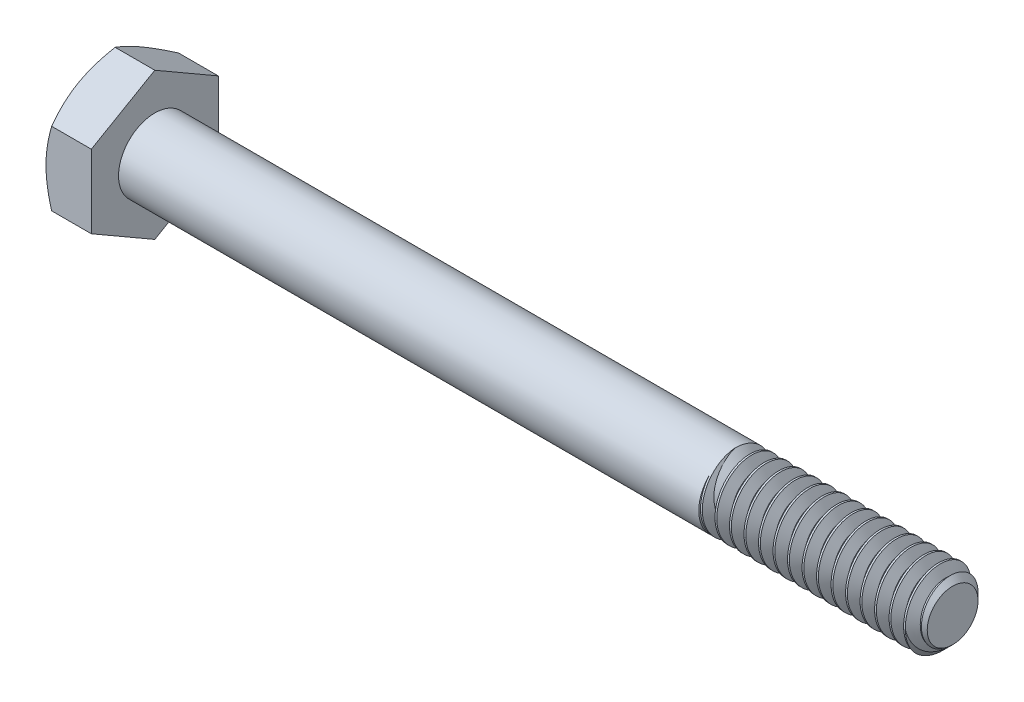
SolidWorks part; units mm, degrees
ref_plane "Front Plane" through (0, 0, 0) normal (0, 0, 1) x (1, 0, 0)
ref_plane "Top Plane" through (0, 0, 0) normal (0, 1, 0) x (1, 0, 0)
ref_plane "Right Plane" through (0, 0, 0) normal (1, 0, 0) x (0, 0, -1)
sketch "Sketch1" plane through (0, 0, 0) normal (0, 0, 1) x (1, 0, 0)
  line L0 (-36.9094, 0) -> (36.9094, 0) construction
  line L1 (36.9094, 3.175) -> (36.9094, -3.175) construction
  line L2 (-32.9406, 5.5563) -> (-32.9406, -5.5563) construction
  line L3 (-36.9094, 5.5562) -> (-36.9094, -5.5562) construction
  point P9 (-32.9406, 0)
  point P10 (32.4644, -3.175)
  dimension "Screw Dia" = 6.35
  dimension "Hex" = 11.1125
  dimension "Head Ht" = 3.9688
  dimension "Screw Lenght" = 69.85
  dimension "D1" = 4.445
ref_plane "Plane2" through (36.9094, 0, 0) normal (1, 0, 0) x (0, 0, -1)
sketch "Sketch5" plane through (36.9094, 0, 0) normal (1, 0, 0) x (0, 0, -1)
  circle A0 centre (0, 0) radius 3.175
extrude "Boss-Extrude3" add sketch "Sketch5" against normal up to vertex (69.85 mm away) up to point (-32.9406, 0, 0)
sketch "Sketch9" plane through (36.9094, 0, 0) normal (1, 0, 0) x (0, 0, -1)
  circle A1 centre (0, 0) radius 3.175
  circle A2 centre (0, 0) radius 3.175
  dimension "D1" = 0
curve "Helix/Spiral1" pitch 1.27 height 20.32 turns 16 parameters "Pitch"=1.27
chamfer "Chamfer1" distance 0.9525 angle 45 1 edges at (36.9094, 0, -3.175)
sketch "Sketch10" plane through (0, 0, 0) normal (0, 0, 1) x (1, 0, 0)
  line L0 (36.9094, 3.175) -> (37.3856, 2.3501)
  line L1 (37.3856, 2.3501) -> (37.5444, 2.3501)
  line L2 (37.5444, 2.3501) -> (38.0206, 3.175)
  line L3 (36.9094, 3.175) -> (38.0206, 3.175)
  line L4 (37.465, 3.175) -> (37.465, 2.3501) construction
  line L5 (37.1475, 2.7626) -> (37.7825, 2.7626) construction
  dimension "D1" = 60
  dimension "D2" = 0.1588
  dimension "D3" = 0.635
sweep "Cut-Sweep1" cut profiles "Sketch10" path "Helix/Spiral1" align with end faces yes
sketch "Sketch11" plane through (0, 0, 0) normal (0, 0, 1) x (1, 0, 0)
  line L0 (-32.9406, 3.175) -> (-32.9406, 0)
  line L1 (-32.9406, 0) -> (21.0344, 0)
  line L3 (21.0344, 0) -> (17.8594, 3.175)
  line L4 (-32.9406, 3.175) -> (17.8594, 3.175)
  dimension "D1" = 45
  dimension "MIn Thread" = 19.05
revolve "Revolve1" add sketch "Sketch11" angle 360 about L1
sketch "Sketch6" plane through (-32.9406, 0, 0) normal (-1, 0, 0) x (0, 0, 1)
  line L0 (0, 5.5563) -> (0, -5.5563) construction
  line L1 (5.5562, 3.2079) -> (0, 6.4158)
  line L2 (0, 6.4158) -> (-5.5562, 3.2079)
  line L3 (-5.5562, 3.2079) -> (-5.5562, -3.2079)
  line L4 (-5.5562, -3.2079) -> (0, -6.4158)
  line L5 (0, -6.4158) -> (5.5562, -3.2079)
  line L6 (5.5562, -3.2079) -> (5.5562, 3.2079)
  circle A0 centre (0, 0) radius 5.5563 construction
extrude "Boss-Extrude4" add sketch "Sketch6" along normal up to vertex (3.9688 mm away) up to point (-36.9094, -5.5562, 0)
sketch "Sketch7" plane through (-36.9094, 0, 0) normal (-1, 0, 0) x (0, 0, 1)
  circle A0 centre (0, 0) radius 5.5563 construction
  circle A1 centre (0, 0) radius 5.5563
sketch "Sketch8" plane through (-36.9094, 0, 0) normal (-1, 0, 0) x (0, 0, 1)
  circle A0 centre (0, 0) radius 5.5563 construction
  circle A1 centre (0, 0) radius 5.5563
extrude "Cut-Extrude3" cut sketch "Sketch8" against normal through all draft 60 flip side to cut
equation "\"D2@Sketch10\" = \"Pitch@Helix/Spiral1\"*.125"
equation "\"D3@Sketch10\" = \"Pitch@Helix/Spiral1\"*.5"
equation "\"D3@Helix/Spiral1\" = \"MIn Thread@Sketch11\"+\"Pitch@Helix/Spiral1\""
equation "\"D1@Chamfer1\" = \"Pitch@Helix/Spiral1\"*.75"
equation "\"D1@Sketch1\" = \"Pitch@Helix/Spiral1\"*3.5"
